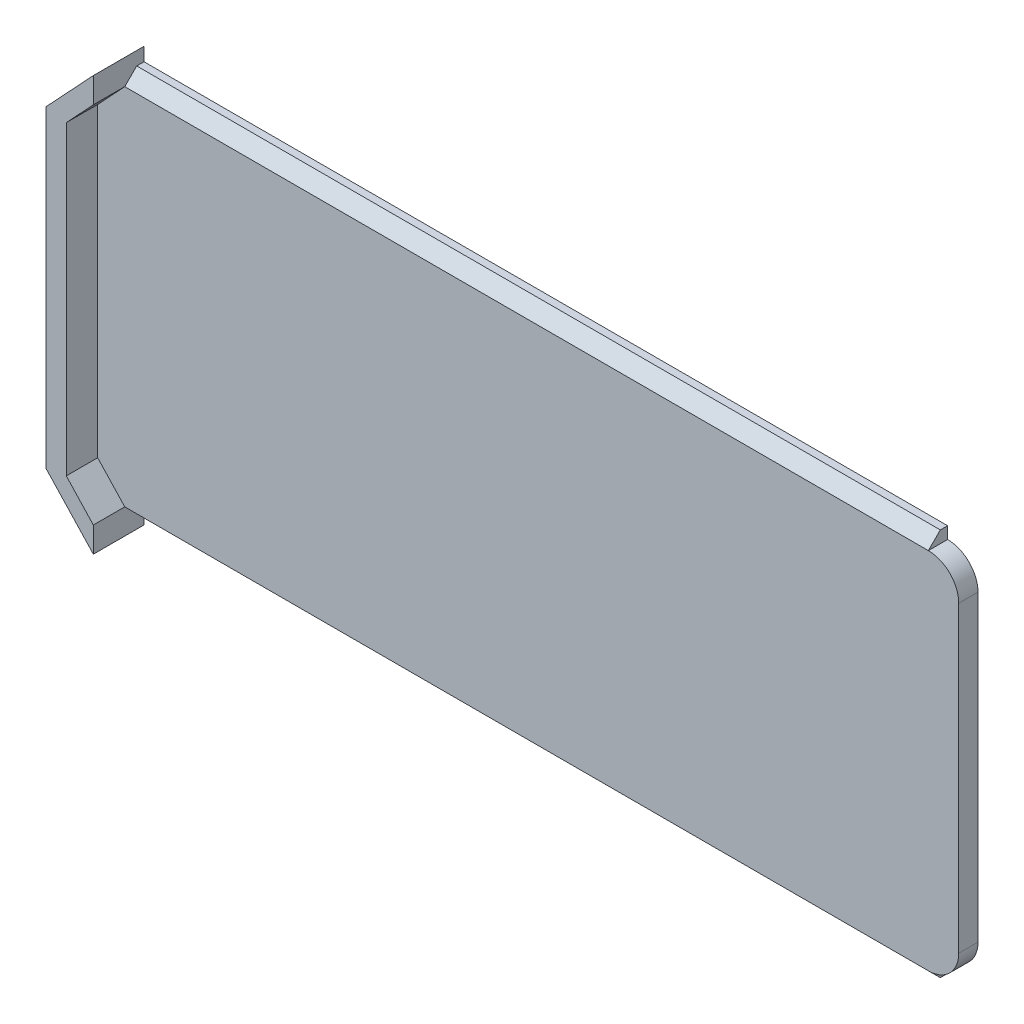
SolidWorks part; units mm, degrees
ref_plane "Front Plane" through (0, 0, 0) normal (0, 0, 1) x (1, 0, 0)
ref_plane "Top Plane" through (0, 0, 0) normal (0, 1, 0) x (1, 0, 0)
ref_plane "Right Plane" through (0, 0, 0) normal (1, 0, 0) x (0, 0, -1)
sketch "Sketch3" plane through (0, 0, 0) normal (0, 0, 1) x (1, 0, 0)
  line L0 (-37.8284, -36.25) -> (-37.8284, -38.75)
  line L1 (-37.8284, -38.75) -> (-40.5, -41.6091)
  line L2 (-40.5, -41.6091) -> (-40.5, -71.8006)
  line L3 (-40.5, -71.8006) -> (-37.8284, -74.66)
  line L4 (-37.8284, -74.66) -> (-37.8284, -77.16)
  line L8 (-37.8284, -36.25) -> (-42.5, -41.2496)
  line L9 (-42.5, -41.2496) -> (-42.5, -72.16)
  line L10 (-42.5, -72.16) -> (-37.8284, -77.16)
  line L13 (-37.8284, -38.75) -> (41.4716, -38.75)
  line L15 (-37.8284, -74.66) -> (41.4716, -74.66)
  line L16 (44.4716, -41.75) -> (44.4716, -71.66)
  arc A0 (44.4716, -71.66) -> (41.4716, -74.66) centre (41.4716, -71.66) cw
  arc A1 (44.4716, -41.75) -> (41.4716, -38.75) centre (41.4716, -41.75) ccw
  point P11 (44.4716, -74.66)
  point P12 (44.4716, -38.75)
  dimension "D1" = 3
  dimension "D2" = 2
  dimension "D3" = 2.5
  dimension "D4" = 35.91
  dimension "D5" = 2.5
extrude "Boss-Extrude1" add sketch "Sketch3" along normal blind 1.9 contours L9 L10 L4 L3 L2 L1 L0 L8 | L15 L16 L13 L1 L2 L3 region at (-41.0894, -56.7048, 0) region at (2.0372, -56.705, 0)
extrude "Boss-Extrude2" add sketch "Sketch3<5>" along normal blind 5 contours L9 L10 L4 L3 L2 L1 L0 L8 region at (-41.0894, -56.7048, 0)
sketch "Sketch3<5>" plane through (0, 0, 0) normal (0, 0, 1) x (1, 0, 0) same geometry as "Sketch3"
sketch "Sketch4" plane through (0, -74.66, 0) normal (0, -1, 0) x (1, 0, 0)
  line L4 (-37.8284, 0) -> (41.4716, 0)
  line L5 (41.4716, 0) -> (41.4716, 1.9)
  line L6 (41.4716, 1.9) -> (-37.8284, 1.9)
  line L7 (-37.8284, 1.9) -> (-37.8284, 0)
  line L8 (-37.8284, 0) -> (41.4716, 0)
  line L10 (41.4716, 1.9) -> (-37.8284, 1.9)
  line L11 (-37.8284, 1.9) -> (-37.8284, 0)
  line L12 (41.4716, 0) -> (41.4716, 1.9)
  dimension "D1" = 0
extrude "Boss-Extrude3" add sketch "Sketch4" along normal blind 1.18
sketch "Sketch5" plane through (0, -38.75, 0) normal (0, 1, 0) x (1, 0, 0)
  line L4 (41.4716, 0) -> (-37.8284, 0)
  line L5 (-37.8284, 0) -> (-37.8284, -1.9)
  line L6 (-37.8284, -1.9) -> (41.4716, -1.9)
  line L7 (41.4716, -1.9) -> (41.4716, 0)
  line L8 (41.4716, 0) -> (-37.8284, 0)
  line L9 (-37.8284, 0) -> (-37.8284, -1.9)
  line L10 (-37.8284, -1.9) -> (41.4716, -1.9)
  line L12 (41.4716, -1.9) -> (41.4716, 0)
  dimension "D1" = 0
extrude "Boss-Extrude4" add sketch "Sketch5" along normal blind 1.18
chamfer "Chamfer2" distance 1.18 angle 45 2 edges at (1.8216, -75.84, 1.9) (1.8216, -37.57, 1.9)
